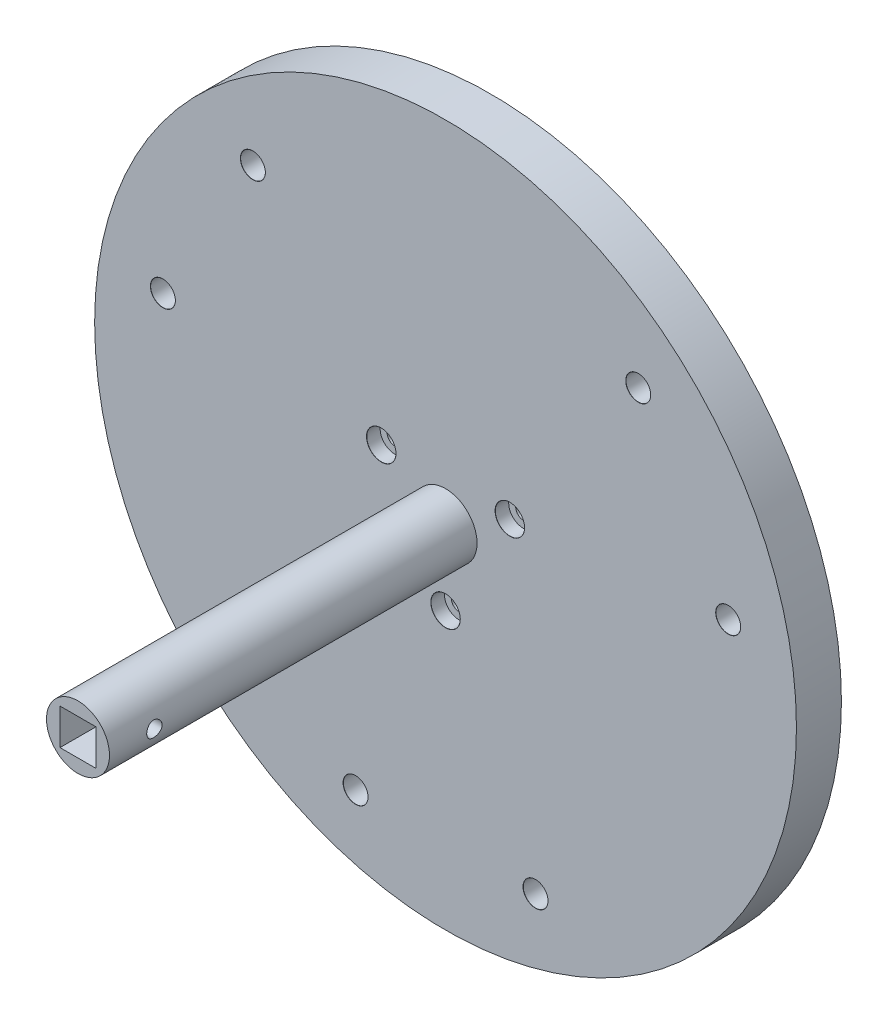
SolidWorks part; units mm, degrees
ref_plane "Front Plane" through (0, 0, 0) normal (0, 0, 1) x (1, 0, 0)
ref_plane "Top Plane" through (0, 0, 0) normal (0, 1, 0) x (1, 0, 0)
ref_plane "Right Plane" through (0, 0, 0) normal (1, 0, 0) x (0, 0, -1)
sketch "Sketch1" plane through (0, 0, 0) normal (0, 0, 1) x (1, 0, 0)
  circle A0 centre (0, 0) radius 78
  dimension "D1" = 156
extrude "Boss-Extrude1" add sketch "Sketch1" along normal blind 10
sketch "Sketch14" plane through (0, 0, 10) normal (0, 0, 1) x (1, 0, 0)
ref_axis "Axis2" through (0, 0, 38.9853) along (0, 0, -1)
sketch "Sketch2" plane through (0, 0, 10) normal (0, 0, 1) x (1, 0, 0)
  line L0 (0, 0) -> (0, -16.5) construction
  line L1 (-14.2894, 8.25) -> (0, 0) construction
  line L2 (0, 0) -> (14.2894, 8.25) construction
  circle A0 centre (0, 0) radius 16.5 construction
  point P7 (-14.2894, 8.25)
  point P8 (14.2894, 8.25)
  point P9 (0, -16.5)
  dimension "D1" = 33
  dimension "D2" = 120
  dimension "D3" = 120
sketch "Sketch5" plane through (0, 0, 10) normal (0, 0, 1) x (1, 0, 0)
  point P0 (-14.2894, 8.25)
  point P3 (14.2894, 8.25)
  point P6 (0, -16.5)
hole_wizard "CBORE for M3 SHCS1" positions "Sketch5" profile "Sketch4" counterbore size "M3" standard "ANSI Metric" end condition up to next
sketch "Sketch4" plane through (-14.2894, 8.25, 10) normal (1, 0, 0) x (0, -1, 0)
  line L0 (0, 0) -> (0, 10)
  line L1 (0, 10) -> (1.7, 10)
  line L3 (1.7, 10) -> (1.7, 3)
  line L4 (3.25, 3) -> (1.7, 3)
  line L5 (3.25, 3) -> (3.25, 0.025)
  line L6 (3.25, 0.025) -> (3.275, 0)
  line L7 (3.275, 0) -> (0, 0)
  line L8 (-3.25, 0.025) -> (-3.275, 0) construction
  line L11 (0, -6.35) -> (0, 107.95) construction
  dimension "Thru Hole Dia." = 3.4
  dimension "Thru Hole Depth" = 10
  dimension "C'Bore Dia." = 6.5
  dimension "C'Bore Depth" = 3
  dimension "Near C'Sink Dia." = 6.55
  dimension "Near C'Sink Angle" = 90
sketch "Sketch6" plane through (0, 0, 10) normal (0, 0, 1) x (1, 0, 0)
  circle A0 centre (0, 0) radius 7
  dimension "D1" = 14
extrude "Boss-Extrude2" add sketch "Sketch6" along normal blind 81.7
sketch "Sketch20" plane through (0, 0, 91.7) normal (0, 0, 1) x (1, 0, 0)
  line L1 (-4, 4) -> (4, 4)
  line L2 (-4, 4) -> (-4, -4)
  line L3 (-4, -4) -> (4, -4)
  line L4 (4, 4) -> (4, -4)
  line L5 (-4, 4) -> (4, -4) construction
  line L6 (-4, -4) -> (4, 4) construction
  point P0 (0, 0)
  dimension "D1" = 8
extrude "Cut-Extrude1" cut sketch "Sketch20" against normal blind 20
sketch "Sketch27" plane through (0, 0, 10) normal (0, 0, 1) x (1, 0, 0)
  line L0 (-20, -61) -> (20, -61) construction
  line L2 (0, 0) -> (0, -78) construction
  circle A0 centre (0, 0) radius 78 construction
  point P0 (-20, -61)
  point P2 (20, -61)
  point P17 (0, -61)
  dimension "D1" = 40
  dimension "D2" = 61
hole_wizard "M5 Clearance Hole3" positions "Sketch27" profile "Sketch26" hole size "M5" standard "ANSI Metric" end condition up to next
sketch "Sketch26" plane through (-20, -61, 10) normal (1, 0, 0) x (0, -1, 0)
  line L0 (0, 0) -> (0, 10)
  line L1 (0, 10) -> (2.75, 10)
  line L2 (2.75, 10) -> (2.75, 0.025)
  line L3 (2.75, 0.025) -> (2.775, 0)
  line L5 (2.775, 0) -> (0, 0)
  line L6 (-2.75, 0.025) -> (-2.775, 0) construction
  line L11 (0, -6.35) -> (0, 107.95) construction
  dimension "Thru Hole Dia." = 5.5
  dimension "Thru Hole Depth" = 10
  dimension "Near C'Sink Dia." = 5.55
  dimension "Near C'Sink Angle" = 90
pattern_circular "CirPattern1" count 3 over 360 about axis through (0, 0, 38.9853) along (0, 0, -1) of "M5 Clearance Hole3"
ref_plane "Plane1" through (7, 0, 0) normal (1, 0, 0) x (0, 0, -1)
sketch "Sketch34" plane through (7, 0, 0) normal (1, 0, 0) x (0, 0, -1)
  line L0 (-91.7, 7) -> (-91.7, -7) construction
  line L1 (-91.7, 7) -> (-91.7, -7) construction
  point P0 (-81.7, 0)
  point P10 (-91.7, 0)
  point P11 (-91.7, -4.0849)
  point P12 (-91.7, -7)
  point P13 (-91.7, -4.8733)
  point P15 (0, 0)
  dimension "D1" = 10
hole_wizard "M3 Clearance Hole2" positions "Sketch34" profile "Sketch33" hole size "M3" standard "ANSI Metric" end condition through all
sketch "Sketch33" plane through (7, 0, 81.7) normal (0, 1, 0) x (0, 0, -1)
  line L0 (0, 0) -> (0, 85)
  line L1 (0, 85) -> (1.7, 85)
  line L2 (1.7, 85) -> (1.7, 0.025)
  line L3 (1.7, 0.025) -> (1.725, 0)
  line L5 (1.725, 0) -> (0, 0)
  line L6 (-1.7, 0.025) -> (-1.725, 0) construction
  line L11 (0, -6.35) -> (0, 107.95) construction
  dimension "Thru Hole Dia." = 3.4
  dimension "Thru Hole Depth" = 85
  dimension "Near C'Sink Dia." = 3.45
  dimension "Near C'Sink Angle" = 90
